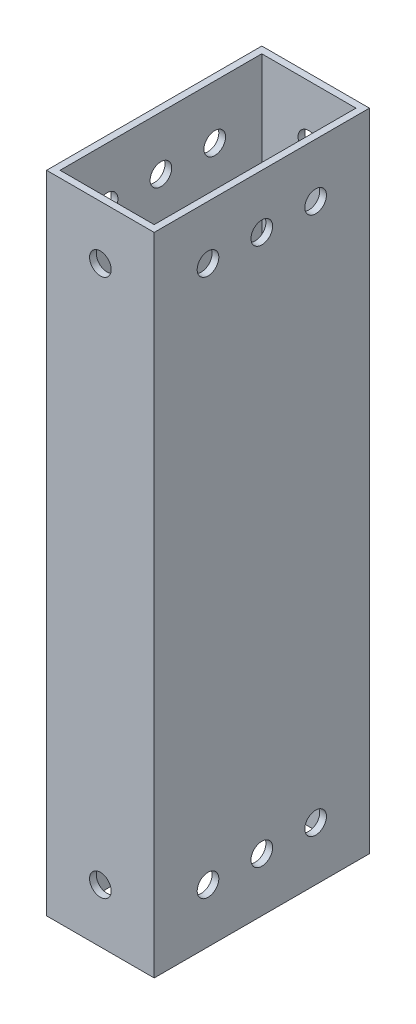
SolidWorks part; units mm, degrees
material "6061-T6 (SS)"
ref_plane "Front" through (0, 0, 0) normal (0, 0, 1) x (1, 0, 0)
ref_plane "Top" through (0, 0, 0) normal (0, 1, 0) x (1, 0, 0)
ref_plane "Right" through (0, 0, 0) normal (1, 0, 0) x (0, 0, -1)
sketch "Sketch1" plane through (0, 0, 0) normal (0, 1, 0) x (1, 0, 0)
  line L1 (12.7, 25.4) -> (-12.7, 25.4)
  line L2 (12.7, 25.4) -> (12.7, -25.4)
  line L3 (12.7, -25.4) -> (-12.7, -25.4)
  line L4 (-12.7, 25.4) -> (-12.7, -25.4)
  line L5 (12.7, 25.4) -> (-12.7, -25.4) construction
  line L6 (12.7, -25.4) -> (-12.7, 25.4) construction
  point P0 (0, 0)
  dimension "D1" = 25.4
  dimension "D2" = 50.8
extrude "Extrude-Thin1" add sketch "Sketch1" along normal up to surface (152.4 mm away) thin thin type one direction reverse wall 1.5875
sketch "Sketch4" plane through (-12.7, 0, 0) normal (-1, 0, 0) x (0, 0, 1)
  line L0 (-12.7, 12.7) -> (12.7, 12.7) construction
  line L3 (-12.7, 139.7) -> (12.7, 139.7) construction
  line L5 (-25.4, 0) -> (25.4, 0) construction
  line L6 (-25.4, 152.4) -> (25.4, 152.4) construction
  point P0 (-12.7, 139.7)
  point P2 (0, 139.7)
  point P4 (12.7, 139.7)
  point P6 (-12.7, 12.7)
  point P8 (0, 12.7)
  point P10 (12.7, 12.7)
  point P25 (0, 0)
  dimension "D1" = 12.7
  dimension "D2" = 12.7
  dimension "D3" = 12.7
  dimension "D4" = 12.7
hole_wizard "#10 Clearance Hole1" positions "Sketch4" profile "Sketch3" hole size "#10" standard "ANSI Inch" end condition through all
sketch "Sketch3" plane through (-12.7, 139.7, -12.7) normal (0, 1, 0) x (0, 0, 1)
  line L0 (0, 0) -> (0, 25.4)
  line L1 (0, 25.4) -> (2.5527, 25.4)
  line L2 (2.5527, 25.4) -> (2.5527, 0)
  line L5 (2.5527, 0) -> (0, 0)
  line L11 (0, -6.35) -> (0, 107.95) construction
  dimension "Thru Hole Dia." = 5.1054
  dimension "Thru Hole Depth" = 25.4
sketch "Sketch7" plane through (0, 0, 25.4) normal (0, 0, 1) x (1, 0, 0)
  line L0 (-12.7, 0) -> (12.7, 0) construction
  line L1 (-12.7, 152.4) -> (12.7, 152.4) construction
  point P0 (0, 12.7)
  point P2 (0, 139.7)
  dimension "D1" = 12.7
  dimension "D2" = 12.7
hole_wizard "#10 Clearance Hole2" positions "Sketch7" profile "Sketch6" hole size "#10" standard "ANSI Inch" end condition through all
sketch "Sketch6" plane through (0, 12.7, 25.4) normal (1, 0, 0) x (0, -1, 0)
  line L0 (0, 0) -> (0, 50.8)
  line L1 (0, 50.8) -> (2.5527, 50.8)
  line L2 (2.5527, 50.8) -> (2.5527, 0)
  line L5 (2.5527, 0) -> (0, 0)
  line L11 (0, -6.35) -> (0, 107.95) construction
  dimension "Thru Hole Dia." = 5.1054
  dimension "Thru Hole Depth" = 50.8
